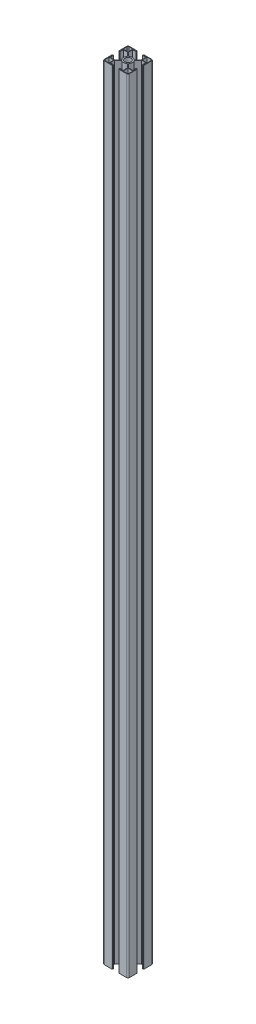
SolidWorks part; units mm, degrees
ref_plane "Plano frontal" through (0, 0, 0) normal (0, 0, 1) x (1, 0, 0)
ref_plane "Plano superior" through (0, 0, 0) normal (0, 1, 0) x (1, 0, 0)
ref_plane "Plano direito" through (0, 0, 0) normal (1, 0, 0) x (0, 0, -1)
sketch "Esboço1" plane through (0, 0, 0) normal (0, 1, 0) x (1, 0, 0)
  line L1 (-18, -20) -> (-5, -20)
  line L2 (-20, -18) -> (-20, -5)
  line L3 (-18, 20) -> (-5, 20)
  line L4 (20, -18) -> (20, -5)
  line L5 (-20, -20) -> (-11.25, -11.25) construction
  line L6 (-20, 20) -> (-11.25, 11.25) construction
  line L7 (11.25, 11.25) -> (20, 20) construction
  line L8 (11.25, -11.25) -> (20, -20) construction
  line L9 (-4.9497, 4.9497) -> (4.9497, -4.9497) construction
  line L10 (0, 20) -> (0, -20) construction
  line L11 (-10.5, -11.2067) -> (-10.5, -18)
  line L12 (-10.5, -18) -> (-5, -18)
  line L13 (-5, -18) -> (-5, -20)
  line L14 (-11.2067, -10.5) -> (-18, -10.5)
  line L15 (-18, -10.5) -> (-18, -5)
  line L16 (-18, -5) -> (-20, -5)
  line L18 (5, -20) -> (18, -20)
  line L19 (20, -5) -> (20, -18)
  line L20 (18, -5) -> (20, -5)
  line L21 (-20, -5) -> (-20, -18)
  line L22 (-5, -20) -> (-18, -20)
  line L23 (18, -10.5) -> (18, -5)
  line L24 (11.2067, -10.5) -> (18, -10.5)
  line L25 (5, -18) -> (5, -20)
  line L26 (10.5, -18) -> (5, -18)
  line L27 (10.5, -11.2067) -> (10.5, -18)
  line L28 (-20, 0) -> (20, 0) construction
  line L31 (10.5, 11.2067) -> (10.5, 18)
  line L32 (10.5, 18) -> (5, 18)
  line L33 (5, 18) -> (5, 20)
  line L34 (11.2067, 10.5) -> (18, 10.5)
  line L35 (18, 10.5) -> (18, 5)
  line L36 (-5, 20) -> (-18, 20)
  line L37 (-20, 5) -> (-20, 18)
  line L38 (18, 5) -> (20, 5)
  line L39 (20, 5) -> (20, 18)
  line L40 (5, 20) -> (18, 20)
  line L41 (-18, 5) -> (-20, 5)
  line L42 (-18, 10.5) -> (-18, 5)
  line L43 (-11.2067, 10.5) -> (-18, 10.5)
  line L44 (-5, 18) -> (-5, 20)
  line L45 (-10.5, 18) -> (-5, 18)
  line L46 (-10.5, 11.2067) -> (-10.5, 18)
  line L48 (-18, 20) -> (-5, 20)
  line L49 (-19.25, 5.75) -> (-18.75, 5.75)
  line L50 (-18.75, 5.75) -> (-18.75, 11.25)
  line L51 (-18.75, 11.25) -> (-11.25, 11.25)
  line L52 (-11.25, 11.25) -> (-11.25, 18.75)
  line L53 (-11.25, 18.75) -> (-5.75, 18.75)
  line L54 (-5.75, 18.75) -> (-5.75, 19.25)
  line L55 (-5.75, 19.25) -> (-17.4697, 19.25)
  line L56 (-19.25, 5.75) -> (-19.25, 17.4697)
  line L58 (19.25, 5.75) -> (19.25, 17.4697)
  line L59 (5.75, 19.25) -> (17.4697, 19.25)
  line L60 (5.75, 18.75) -> (5.75, 19.25)
  line L61 (11.25, 18.75) -> (5.75, 18.75)
  line L62 (11.25, 11.25) -> (11.25, 18.75)
  line L63 (18.75, 11.25) -> (11.25, 11.25)
  line L64 (18.75, 5.75) -> (18.75, 11.25)
  line L65 (19.25, 5.75) -> (18.75, 5.75)
  line L66 (10.5, 11.2067) -> (10.5, 18)
  line L67 (10.5, 18) -> (5, 18)
  line L68 (5, 18) -> (5, 20)
  line L69 (11.2067, 10.5) -> (18, 10.5)
  line L70 (18, 10.5) -> (18, 5)
  line L71 (18, 5) -> (20, 5)
  line L72 (20, 5) -> (20, 18)
  line L73 (5, 20) -> (18, 20)
  line L77 (5, -20) -> (18, -20)
  line L78 (20, -5) -> (20, -18)
  line L79 (18, -5) -> (20, -5)
  line L80 (18, -10.5) -> (18, -5)
  line L81 (11.2067, -10.5) -> (18, -10.5)
  line L82 (5, -18) -> (5, -20)
  line L83 (10.5, -18) -> (5, -18)
  line L84 (10.5, -11.2067) -> (10.5, -18)
  line L85 (19.25, -5.75) -> (18.75, -5.75)
  line L86 (18.75, -5.75) -> (18.75, -11.25)
  line L87 (18.75, -11.25) -> (11.25, -11.25)
  line L88 (11.25, -11.25) -> (11.25, -18.75)
  line L89 (11.25, -18.75) -> (5.75, -18.75)
  line L90 (5.75, -18.75) -> (5.75, -19.25)
  line L91 (5.75, -19.25) -> (17.4697, -19.25)
  line L92 (19.25, -5.75) -> (19.25, -17.4697)
  line L93 (-19.25, -5.75) -> (-19.25, -17.4697)
  line L94 (-5.75, -19.25) -> (-17.4697, -19.25)
  line L95 (-5.75, -18.75) -> (-5.75, -19.25)
  line L96 (-11.25, -18.75) -> (-5.75, -18.75)
  line L97 (-11.25, -11.25) -> (-11.25, -18.75)
  line L98 (-18.75, -11.25) -> (-11.25, -11.25)
  line L99 (-18.75, -5.75) -> (-18.75, -11.25)
  line L100 (-19.25, -5.75) -> (-18.75, -5.75)
  line L101 (-18, -20) -> (-5, -20)
  line L103 (-10.5, -11.2067) -> (-10.5, -18)
  line L104 (-10.5, -18) -> (-5, -18)
  line L105 (-5, -18) -> (-5, -20)
  line L106 (-11.2067, -10.5) -> (-18, -10.5)
  line L107 (-18, -10.5) -> (-18, -5)
  line L108 (-18, -5) -> (-20, -5)
  line L109 (5, -20) -> (18, -20)
  line L110 (20, -5) -> (20, -18)
  line L111 (18, -5) -> (20, -5)
  line L112 (-20, -5) -> (-20, -18)
  line L113 (-5, -20) -> (-18, -20)
  line L114 (18, -10.5) -> (18, -5)
  line L115 (11.2067, -10.5) -> (18, -10.5)
  line L116 (5, -18) -> (5, -20)
  line L117 (10.5, -18) -> (5, -18)
  line L118 (10.5, -11.2067) -> (10.5, -18)
  line L119 (-18, -20) -> (-5, -20)
  line L121 (-4.5838, 5.2904) -> (-10.5, 11.2067)
  line L122 (-5.2904, 4.5838) -> (-11.2067, 10.5)
  line L123 (-5.2904, -4.5838) -> (-11.2067, -10.5)
  line L124 (-4.5838, -5.2904) -> (-10.5, -11.2067)
  line L129 (4.5838, -5.2904) -> (10.5, -11.2067)
  line L130 (5.2904, -4.5838) -> (11.2067, -10.5)
  line L131 (5.2904, 4.5838) -> (11.2067, 10.5)
  line L132 (4.5838, 5.2904) -> (10.5, 11.2067)
  line L133 (5, 20) -> (18, 20)
  line L134 (5, 20) -> (18, 20)
  line L135 (-20, 5) -> (-20, 18)
  line L136 (20, 5) -> (20, 18)
  line L137 (5, -20) -> (18, -20)
  line L138 (5, -20) -> (18, -20)
  line L139 (5, -20) -> (18, -20)
  line L141 (-4.9497, -4.9497) -> (4.9497, 4.9497) construction
  arc A0 (5.2904, -4.5838) -> (5.2904, 4.5838) centre (0, 0) ccw
  arc A1 (-18, -20) -> (-20, -18) centre (-18, -18) cw
  arc A2 (18, -20) -> (20, -18) centre (18, -18) ccw
  arc A3 (18, 20) -> (20, 18) centre (18, 18) cw
  arc A4 (-20, 18) -> (-18, 20) centre (-18, 18) cw
  circle A5 centre (0, 0) radius 5
  arc A6 (18, -20) -> (20, -18) centre (18, -18) ccw
  arc A7 (18, 20) -> (20, 18) centre (18, 18) cw
  arc A8 (18, 20) -> (20, 18) centre (18, 18) cw
  arc A9 (-18, 20) -> (-20, 18) centre (-18, 18) ccw
  arc A10 (-19.25, 17.4697) -> (-17.4697, 19.25) centre (-17.4697, 17.4697) cw
  arc A11 (19.25, 17.4697) -> (17.4697, 19.25) centre (17.4697, 17.4697) ccw
  arc A12 (18, 20) -> (20, 18) centre (18, 18) cw
  arc A13 (20, 18) -> (18, 20) centre (18, 18) ccw
  arc A14 (20, -18) -> (18, -20) centre (18, -18) cw
  arc A15 (18, -20) -> (20, -18) centre (18, -18) ccw
  arc A16 (19.25, -17.4697) -> (17.4697, -19.25) centre (17.4697, -17.4697) cw
  arc A17 (-19.25, -17.4697) -> (-17.4697, -19.25) centre (-17.4697, -17.4697) ccw
  arc A18 (-18, -20) -> (-20, -18) centre (-18, -18) cw
  arc A19 (18, -20) -> (20, -18) centre (18, -18) ccw
  arc A20 (18, -20) -> (20, -18) centre (18, -18) ccw
  arc A21 (-20, -18) -> (-18, -20) centre (-18, -18) ccw
  arc A22 (18, -20) -> (20, -18) centre (18, -18) ccw
  arc A23 (-4.5838, -5.2904) -> (4.5838, -5.2904) centre (0, 0) ccw
  arc A24 (-5.2904, 4.5838) -> (-5.2904, -4.5838) centre (0, 0) ccw
  arc A25 (4.5838, 5.2904) -> (-4.5838, 5.2904) centre (0, 0) ccw
  point P0 (0, 0)
  point P23 (0, 7)
  point P67 (-19, 5)
  dimension "D3" = 2
  dimension "D4" = 14
  dimension "D5" = 10
  dimension "D16" = 0.75
  dimension "D17" = 2
  dimension "D1" = 40
  dimension "D2" = 40
  dimension "D6" = 15
  dimension "D7" = 2
  dimension "D8" = 7.5
  dimension "D11" = 0.75
  dimension "D9" = 0.75
  dimension "D10" = 0.75
  dimension "D12" = 0.75
  dimension "D13" = 0.75
  dimension "D14" = 0.75
  dimension "D15" = 0.75
  dimension "D18" = 5.5
  dimension "D19" = 40
  dimension "D20" = 40
  dimension "D21" = 0.5
  dimension "D22" = 0.5
  dimension "D23" = 0.5
  dimension "D24" = 0.5
  dimension "D25" = 0.5
  dimension "D26" = 0.5
extrude "Ressalto-extrusão1" add sketch "Esboço1" along normal blind 1250 contours L132 A25 L121 L46 L45 L44 L3 A4 L37 L41 L42 L43 L122 A24 L123 L14 L15 L16 L2 A1 L1 L13 L12 L11 L124 A23 L129 L27 L26 L25 L18 A2 L4 L20 L23 L24 L130 A0 L131 L34 L35 L38 L39 A3 L40 L33 L32 L31 L92 A16 region at (-19.0142, 0, 19.0142)
sketch "Esboço4" plane through (0, 1250, 0) normal (0, 1, 0) x (1, 0, 0)
  line L0 (0, -20) -> (0, 20) construction
  line L1 (-5, 20) -> (-5.75, 20)
  line L2 (-5, 20) -> (-5, 19.5)
  line L3 (-5, 19.5) -> (-5.75, 19.5)
  line L4 (-5.75, 20) -> (-5.75, 19.5)
  line L5 (19.5, 5) -> (19.5, 5.75)
  line L6 (-20, 5) -> (-19.5, 5)
  line L7 (-20, 5) -> (-20, 5.75)
  line L8 (-20, 5.75) -> (-19.5, 5.75)
  line L9 (-19.5, 5) -> (-19.5, 5.75)
  line L10 (20, 5.75) -> (19.5, 5.75)
  line L11 (20, 5) -> (20, 5.75)
  line L12 (20, 5) -> (19.5, 5)
  line L13 (5.75, 20) -> (5.75, 19.5)
  line L14 (5, 19.5) -> (5.75, 19.5)
  line L15 (5, 20) -> (5, 19.5)
  line L16 (5, 20) -> (5.75, 20)
  line L17 (20, 0) -> (-20, 0) construction
  line L18 (5, -20) -> (5.75, -20)
  line L19 (5, -20) -> (5, -19.5)
  line L20 (5, -19.5) -> (5.75, -19.5)
  line L21 (5.75, -20) -> (5.75, -19.5)
  line L22 (20, -5) -> (19.5, -5)
  line L23 (20, -5) -> (20, -5.75)
  line L24 (20, -5.75) -> (19.5, -5.75)
  line L25 (-19.5, -5) -> (-19.5, -5.75)
  line L26 (-20, -5.75) -> (-19.5, -5.75)
  line L27 (-20, -5) -> (-20, -5.75)
  line L28 (-20, -5) -> (-19.5, -5)
  line L29 (19.5, -5) -> (19.5, -5.75)
  line L30 (-5.75, -20) -> (-5.75, -19.5)
  line L31 (-5, -19.5) -> (-5.75, -19.5)
  line L32 (-5, -20) -> (-5, -19.5)
  line L33 (-5, -20) -> (-5.75, -20)
  point P10 (0, 0)
  point P26 (0, 0)
  dimension "D1" = 0.75
  dimension "D2" = 0.5
  dimension "D3" = 0.5
  dimension "D4" = 0.75
extrude "Corte-extrusão1" cut sketch "Esboço4" against normal up to surface (1250 mm away) up to face at (14.2043, 0, 14.2043)
